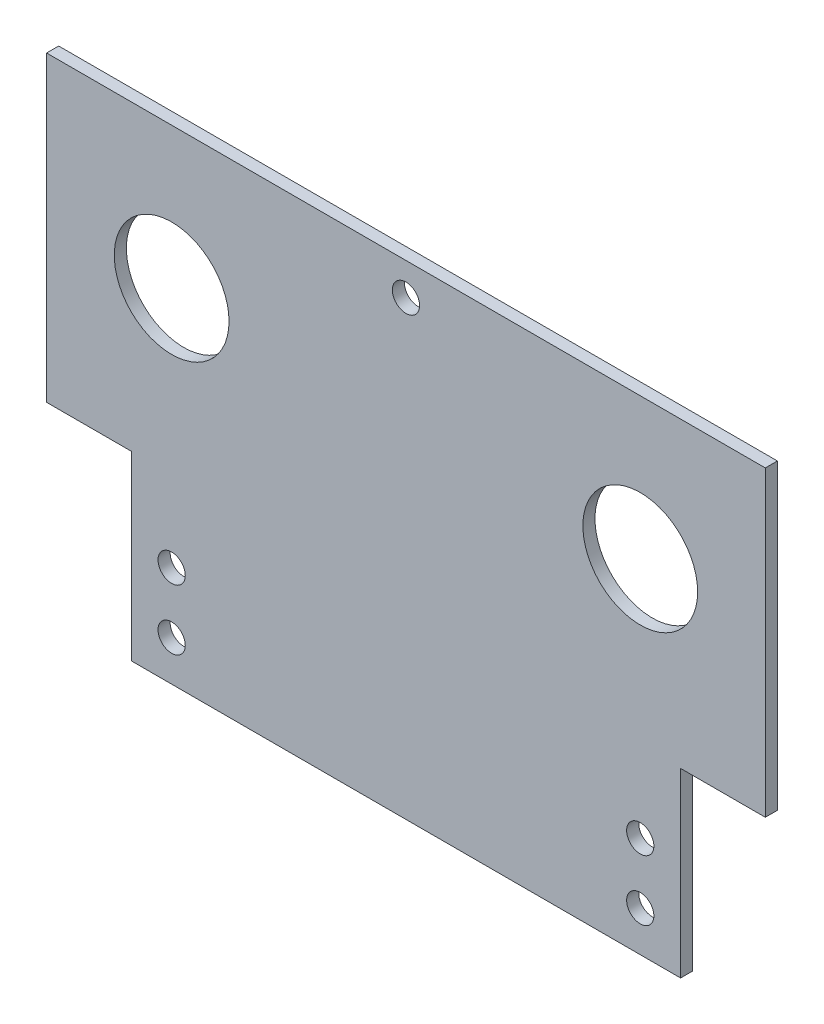
SolidWorks part; units mm, degrees
ref_plane "Front Plane" through (0, 0, 0) normal (0, 0, 1) x (1, 0, 0)
ref_plane "Top Plane" through (0, 0, 0) normal (0, 1, 0) x (1, 0, 0)
ref_plane "Right Plane" through (0, 0, 0) normal (1, 0, 0) x (0, 0, -1)
sketch "Sketch1" plane through (0, 0, 0) normal (0, 0, 1) x (1, 0, 0)
  line L1 (0, 0) -> (178.16, 0)
  line L2 (0, 0) -> (0, -120)
  line L3 (0, -120) -> (178.16, -120)
  line L4 (178.16, 0) -> (178.16, -120)
  dimension "D1" = 120
  dimension "D2" = 178.16
extrude "Boss-Extrude1" add sketch "Sketch1" along normal blind 3
sketch "Sketch2" plane through (0, 0, 3) normal (0, 0, 1) x (1, 0, 0)
  line L0 (0, 0) -> (0, -120) construction
  line L1 (178.16, -120) -> (178.16, 0) construction
  line L2 (0, -120) -> (178.16, -120) construction
  line L3 (178.16, 0) -> (0, 0) construction
  circle A0 centre (31, -35) radius 14.225
  circle A1 centre (147.16, -35) radius 14.225
  circle A3 centre (31, -110) radius 3.375
  circle A4 centre (147.16, -110) radius 3.375
  circle A7 centre (89.08, -8) radius 3.375
  circle A8 centre (31, -95) radius 3.375
  circle A9 centre (147.16, -95) radius 3.375
  point P11 (89.08, 0)
  dimension "D1" = 28.45
  dimension "D2" = 28.45
  dimension "D3" = 10
  dimension "D4" = 6.75
  dimension "D5" = 6.75
  dimension "D7" = 6.75
  dimension "D14" = 6.75
  dimension "D17" = 6.75
  dimension "D9" = 31
  dimension "D10" = 31
  dimension "D12" = 35
  dimension "D13" = 8
  dimension "D15" = 15
  dimension "D16" = 15
extrude "Cut-Extrude1" cut sketch "Sketch2" against normal through all
sketch "Sketch3" plane through (0, 0, 0) normal (0, 0, -1) x (-1, 0, 0)
  line L1 (0, -120) -> (-21, -120)
  line L2 (0, -120) -> (0, -75)
  line L3 (0, -75) -> (-21, -75)
  line L4 (-21, -120) -> (-21, -75)
  line L5 (-178.16, -120) -> (-157.16, -120)
  line L6 (-178.16, -120) -> (-178.16, -75)
  line L7 (-178.16, -75) -> (-157.16, -75)
  line L8 (-157.16, -120) -> (-157.16, -75)
  dimension "D1" = 21
  dimension "D2" = 45
  dimension "D3" = 21
  dimension "D4" = 45
extrude "Cut-Extrude2" cut sketch "Sketch3" against normal through all
